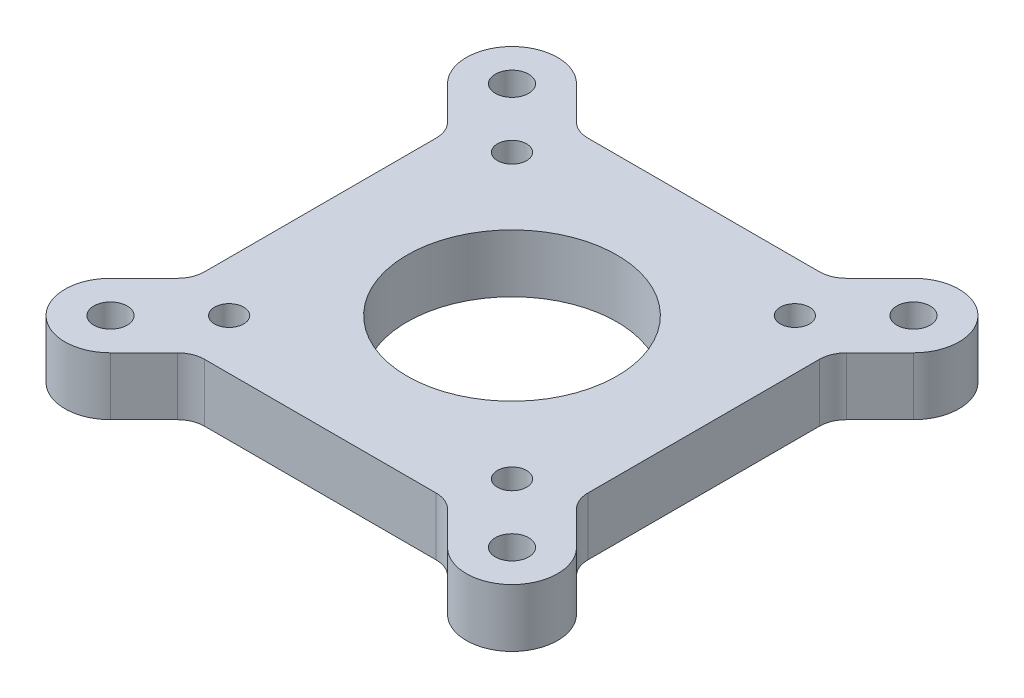
SolidWorks part; units mm, degrees
ref_plane "Front Plane" through (0, 0, 0) normal (0, 0, 1) x (1, 0, 0)
ref_plane "Top Plane" through (0, 0, 0) normal (0, 1, 0) x (1, 0, 0)
ref_plane "Right Plane" through (0, 0, 0) normal (1, 0, 0) x (0, 0, -1)
sketch "Sketch1" plane through (0, 0, 0) normal (0, 1, 0) x (1, 0, 0)
  line L0 (-21, -21) -> (-21, 21)
  line L1 (-21, -21) -> (21, -21)
  line L2 (-21, 21) -> (21, 21)
  line L3 (21, -21) -> (21, 21)
  line L4 (-21, -21) -> (21, 21) construction
  line L5 (-21, 21) -> (21, -21) construction
  point P1 (0, 0)
  dimension "D1" = 42
  dimension "D2" = 42
extrude "Boss-Extrude1" add sketch "Sketch1" along normal blind 6.35
sketch "Sketch2" plane through (0, 6.35, 0) normal (0, 1, 0) x (1, 0, 0)
  line L0 (15.5, -15.5) -> (15.5, 15.5) construction
  line L1 (15.5, -15.5) -> (-15.5, -15.5) construction
  line L2 (15.5, 15.5) -> (-15.5, 15.5) construction
  line L3 (-15.5, -15.5) -> (-15.5, 15.5) construction
  line L4 (15.5, -15.5) -> (-15.5, 15.5) construction
  line L5 (15.5, 15.5) -> (-15.5, -15.5) construction
  point P1 (0, 0)
  dimension "D1" = 31
  dimension "D2" = 31
hole_wizard "M3 Clearance Hole1" positions "Sketch5" profile "Sketch4" hole size "M3" standard "ANSI Metric" end condition through all
sketch "Sketch5" plane through (0, 6.35, 0) normal (0, 1, 0) x (1, 0, 0)
  point P0 (-15.5, 15.5)
  point P3 (-15.5, -15.5)
  point P6 (15.5, -15.5)
  point P9 (15.5, 15.5)
sketch "Sketch4" plane through (-15.5, 6.35, -15.5) normal (1, 0, 0) x (0, 0, 1)
  line L0 (0, 0) -> (0, 6.35)
  line L1 (0, 6.35) -> (1.6, 6.35)
  line L2 (1.6, 6.35) -> (1.6, 0)
  line L5 (1.6, 0) -> (0, 0)
  line L11 (0, -6.35) -> (0, 107.95) construction
  dimension "Thru Hole Dia." = 3.2
  dimension "Thru Hole Depth" = 6.35
sketch "Sketch6" plane through (0, 6.35, 0) normal (0, 1, 0) x (1, 0, 0)
  circle A0 centre (0, 0) radius 11.5
  dimension "D1" = 23
extrude "Cut-Extrude1" cut sketch "Sketch6" against normal through all
sketch "Sketch7" plane through (0, 6.35, 0) normal (0, 1, 0) x (1, 0, 0)
  line L0 (-21, 21) -> (21, -21) construction
  line L1 (-21, 13.9289) -> (-25.5355, 18.4645)
  line L2 (-21, 21) -> (-21, -21) construction
  line L3 (-13.9289, 21) -> (-18.4645, 25.5355)
  line L4 (21, 21) -> (-21, 21) construction
  line L5 (-21, 13.9289) -> (-13.9289, 21) construction
  line L6 (-25.5355, 18.4645) -> (-18.4645, 25.5355) construction
  line L7 (-21, 13.9289) -> (-21, 21)
  line L8 (-21, 21) -> (-13.9289, 21)
  arc A0 (-18.4645, 25.5355) -> (-25.5355, 18.4645) centre (-22, 22) ccw
  line M13 (21, 21) -> (-21, 21)
  line M14 (-21, 21) -> (-21, -21)
  dimension "D2" = 22
  dimension "D1" = 10
extrude "Boss-Extrude2" add sketch "Sketch7" against normal blind 6.35 contours L3 A0 L1 M14 M13 region at (-21.9667, 6.35, -21.9667)
hole_wizard "#6 Clearance Hole1" positions "Sketch10" profile "Sketch9" hole size "#6" standard "ANSI Inch" end condition through all
sketch "Sketch10" plane through (0, 6.35, 0) normal (0, 1, 0) x (1, 0, 0)
  line L0 (-25.5355, 18.4645) -> (-18.4645, 25.5355) construction
  point P1 (-22, 22)
sketch "Sketch9" plane through (-22, 6.35, -22) normal (1, 0, 0) x (0, 0, 1)
  line L0 (0, 0) -> (0, 6.35)
  line L1 (0, 6.35) -> (1.8288, 6.35)
  line L2 (1.8288, 6.35) -> (1.8288, 0)
  line L5 (1.8288, 0) -> (0, 0)
  line L11 (0, -6.35) -> (0, 107.95) construction
  dimension "Thru Hole Dia." = 3.6576
  dimension "Thru Hole Depth" = 6.35
ref_axis "Axis1" through (0, 0, 0) along (0, 1, 0)
pattern_circular "CirPattern2" count 4 over 360 about axis through (0, 0, 0) along (0, 1, 0) of "Boss-Extrude2", "#6 Clearance Hole1"
fillet "Fillet2" radius 3 8 edges at (13.9289, 3.175, -21) (21, 3.175, -13.9289) (21, 3.175, 13.9289) (13.9289, 3.175, 21) (-13.9289, 3.175, 21) (-21, 3.175, 13.9289) (-21, 3.175, -13.9289) (-13.9289, 3.175, -21)
